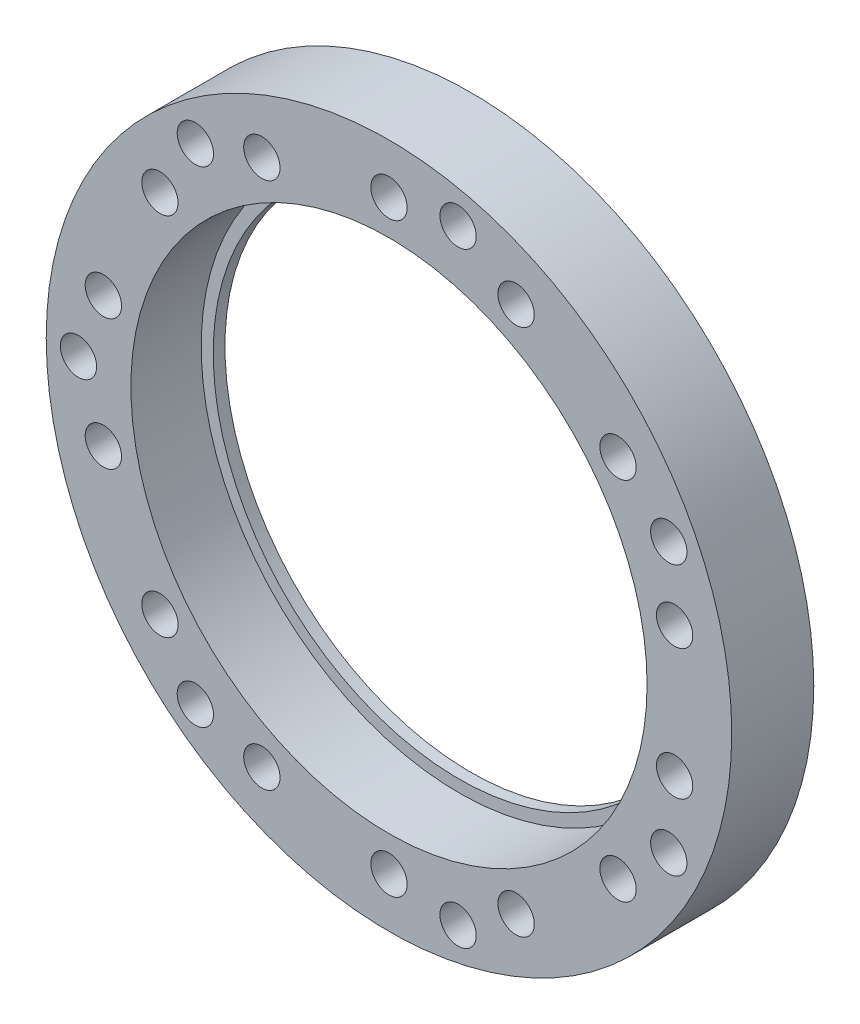
SolidWorks part; units mm, degrees
material "6061 Alloy"
ref_plane "Front Plane" through (0, 0, 0) normal (0, 0, 1) x (1, 0, 0)
ref_plane "Top Plane" through (0, 0, 0) normal (0, 1, 0) x (1, 0, 0)
ref_plane "Right Plane" through (0, 0, 0) normal (1, 0, 0) x (0, 0, -1)
sketch "Sketch1" plane through (0, 0, 0) normal (0, 0, 1) x (1, 0, 0)
  line L0 (0, 0) -> (0, 42.6293) construction
  circle A0 centre (0, 0) radius 22.025
  circle A1 centre (0, 0) radius 29.25
  circle A2 centre (0, 25) radius 1.55
  circle A3 centre (10.8471, 22.5242) radius 1.55
  circle A4 centre (19.5458, 15.5872) radius 1.55
  circle A5 centre (24.3732, 5.563) radius 1.55
  circle A6 centre (24.3732, -5.563) radius 1.55
  circle A7 centre (19.5458, -15.5872) radius 1.55
  circle A8 centre (10.8471, -22.5242) radius 1.55
  circle A9 centre (0, -25) radius 1.55
  circle A10 centre (-10.8471, -22.5242) radius 1.55
  circle A11 centre (-19.5458, -15.5872) radius 1.55
  circle A12 centre (-24.3732, -5.563) radius 1.55
  circle A13 centre (-24.3732, 5.563) radius 1.55
  circle A14 centre (-19.5458, 15.5872) radius 1.55
  circle A15 centre (-10.8471, 22.5242) radius 1.55
  circle A18 centre (0, 0) radius 20
  point P39 (0, 0)
  dimension "D1" = 58.5
  dimension "D2" = 44.05
  dimension "D3" = 3.1
  dimension "D6" = 40
  dimension "D4" = 25
  dimension "D5" = 14
extrude "Boss-Extrude1" add sketch "Sketch1" along normal blind 7 contours A4 | A5 | A6 | A7 | A8 | A9 | A2 L0 | L0 A2 | A3 | A15 | A14 | A12 | A13 | A11 | A10 | A0 A2 A1 A15 A14 A13 A12 A11 A10 A9 A8 A7 A6 A5 A4 A3 region at (20.0979, 20.0979, 0) region at (-0.6578, 25, 0) region at (0.6578, 25, 0) region at (10.8471, 22.5242, 0) region at (19.5458, 15.5872, 0) region at (24.3732, 5.563, 0) region at (24.3732, -5.563, 0) region at (19.5458, -15.5872, 0) region at (10.8471, -22.5242, 0) region at (0, -25, 0) region at (-10.8471, -22.5242, 0) region at (-19.5458, -15.5872, 0) region at (-24.3732, -5.563, 0) region at (-24.3732, 5.563, 0) region at (-19.5458, 15.5872, 0) region at (-10.8471, 22.5242, 0)
extrude "Cut-Extrude1" cut sketch "Sketch1<3>" against normal blind 4 from surface contours A2 L0 | L0 A2 | A3 | A4 | A5 | A6 | A7 | A8 | A9 | A10 | A11 | A12 | A13 | A14 | A15 region at (-0.6578, 25, 0) region at (0.6578, 25, 0) region at (10.8471, 22.5242, 0) region at (19.5458, 15.5872, 0) region at (24.3732, 5.563, 0) region at (24.3732, -5.563, 0) region at (19.5458, -15.5872, 0) region at (10.8471, -22.5242, 0) region at (0, -25, 0) region at (-10.8471, -22.5242, 0) region at (-19.5458, -15.5872, 0) region at (-24.3732, -5.563, 0) region at (-24.3732, 5.563, 0) region at (-19.5458, 15.5872, 0) region at (-10.8471, 22.5242, 0) starting at face at (29.25, 0, 7)
sketch "Sketch1<3>" plane through (0, 0, 0) normal (0, 0, 1) x (1, 0, 0) same geometry as "Sketch1"
sketch "Sketch4" plane through (0, 0, 0) normal (0, 0, 1) x (1, 0, 0)
  circle A0 centre (0, 0) radius 22.25
  circle A1 centre (0, 0) radius 21
  dimension "D1" = 44.5
  dimension "D2" = 42
extrude "Boss-Extrude2" add sketch "Sketch4" along normal blind 1 from surface starting at face at (29.25, 0, 0)
sketch "Sketch2" plane through (0, 0, 0) normal (0, 0, 1) x (1, 0, 0)
  circle A0 centre (0, 0) radius 24
  circle A1 centre (0, 0) radius 29
  dimension "D1" = 48
  dimension "D2" = 58
sketch "Sketch3" plane through (0, 0, 0) normal (0, 0, 1) x (1, 0, 0)
  line L0 (0, 0) -> (0, 31.0844) construction
  line L1 (0, 0) -> (6.9256, 30.3429) construction
  circle A0 centre (0, 0) radius 26.5 construction
  circle A1 centre (5.8968, 25.8356) radius 1.55
  circle A2 centre (23.8757, 11.4979) radius 1.55
  circle A3 centre (23.8757, -11.4979) radius 1.55
  circle A4 centre (5.8968, -25.8356) radius 1.55
  circle A5 centre (-16.5225, -20.7185) radius 1.55
  circle A6 centre (-26.5, 0) radius 1.55
  circle A7 centre (-16.5225, 20.7185) radius 1.55
  point P23 (0, 0)
  dimension "D2" = 53
  dimension "D3" = 3.1
  dimension "D4" = 7
  dimension "D1" = 12.857
extrude "Cut-Extrude2" cut sketch "Sketch3" along normal through all contours A2 | A1 | A7 | A6 | A5 | A4 | A3 region at (5.8968, 25.8356, 0) region at (23.8757, 11.4979, 0) region at (23.8757, -11.4979, 0) region at (5.8968, -25.8356, 0) region at (-16.5225, -20.7185, 0) region at (-26.5, 0, 0) region at (-16.5225, 20.7185, 0)
